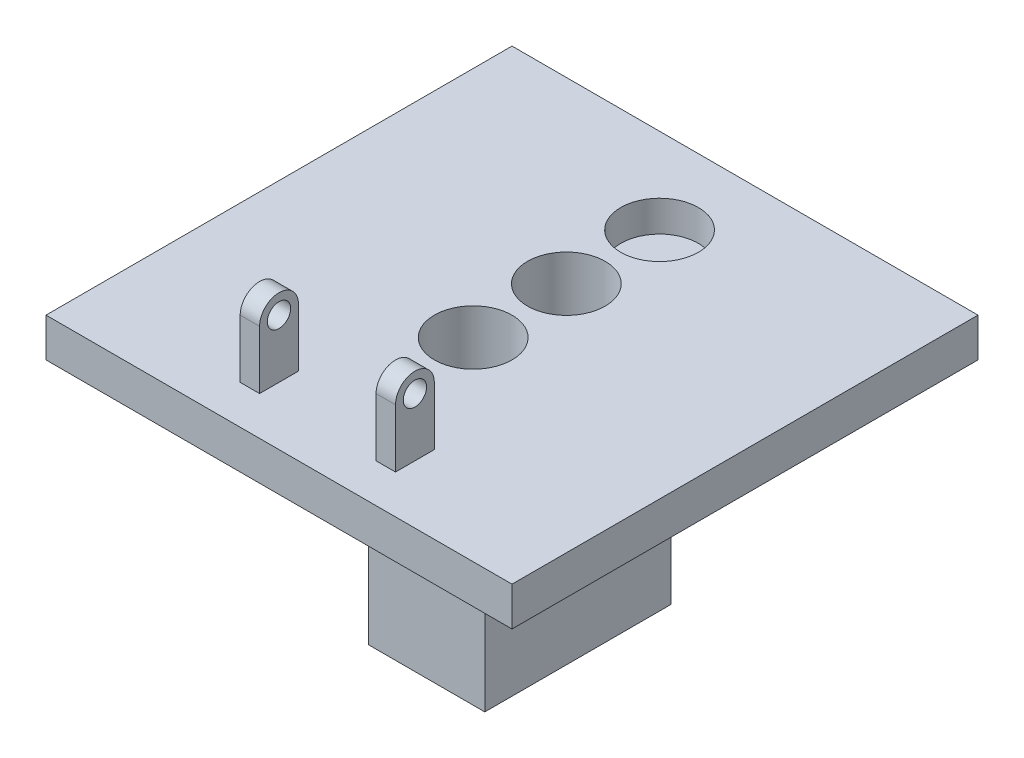
SolidWorks part; units mm, degrees
ref_plane "Front Plane" through (0, 0, 0) normal (0, 0, 1) x (1, 0, 0)
ref_plane "Top Plane" through (0, 0, 0) normal (0, 1, 0) x (1, 0, 0)
ref_plane "Right Plane" through (0, 0, 0) normal (1, 0, 0) x (0, 0, -1)
sketch "Sketch1" plane through (0, 0, 0) normal (0, 1, 0) x (1, 0, 0)
  line L1 (-76.2, 76.2) -> (76.2, 76.2)
  line L2 (-76.2, 76.2) -> (-76.2, -76.2)
  line L3 (-76.2, -76.2) -> (76.2, -76.2)
  line L4 (76.2, 76.2) -> (76.2, -76.2)
  line L5 (-76.2, 76.2) -> (76.2, -76.2) construction
  line L6 (-76.2, -76.2) -> (76.2, 76.2) construction
  point P0 (0, 0)
  dimension "D1" = 152.4
  dimension "D2" = 152.4
extrude "Boss-Extrude1" add sketch "Sketch1" along normal blind 12.7
sketch "Sketch2" plane through (0, 0, 0) normal (1, 0, 0) x (0, 0, -1)
  line L0 (-76.2, 12.7) -> (76.2, 12.7) construction
  line L1 (-63.5, 12.7) -> (-50.8, 12.7)
  line L2 (-63.5, 12.7) -> (-63.5, 38.1)
  line L3 (-63.5, 38.1) -> (-50.8, 38.1)
  line L4 (-50.8, 12.7) -> (-50.8, 38.1)
  line L6 (-76.2, 12.7) -> (-76.2, 0) construction
  dimension "D1" = 25.4
  dimension "D2" = 12.7
  dimension "D3" = 12.7
extrude "Boss-Extrude2" add sketch "Sketch2" along normal mid plane 50.8
fillet "Fillet1" 2 edges at (0, 38.1, 63.5) (0, 38.1, 50.8) type full round first side face at (0, 25.4, 63.5) second side face at (0, 25.4, 50.8) middle face at (0, 38.1, 57.15)
sketch "Sketch3" plane through (0, 0, 63.5) normal (0, 0, 1) x (1, 0, 0)
  line L0 (-76.2, 12.7) -> (76.2, 12.7) construction
  line L1 (-19.05, 12.7) -> (19.05, 12.7)
  line L2 (-19.05, 12.7) -> (-19.05, 48.2361)
  line L3 (-19.05, 48.2361) -> (19.05, 48.2361)
  line L4 (19.05, 12.7) -> (19.05, 48.2361)
  line L5 (-25.4, 31.75) -> (-25.4, 12.7) construction
  line L6 (25.4, 31.75) -> (25.4, 12.7) construction
  dimension "D1" = 6.35
  dimension "D2" = 6.35
extrude "Cut-Extrude1" cut sketch "Sketch3" against normal blind 50.8
sketch "Sketch4" plane through (25.4, 0, 0) normal (1, 0, 0) x (0, 0, -1)
  circle A0 centre (-57.15, 31.75) radius 3.81
  dimension "D1" = 7.62
extrude "Cut-Extrude2" cut sketch "Sketch4" against normal blind 50.8
sketch "Sketch5" plane through (0, 0, 0) normal (1, 0, 0) x (0, 0, -1)
  line L0 (-50.8, 12.7) -> (39.1205, 102.6205) construction
  line L1 (-76.2, 12.7) -> (76.2, 12.7) construction
  dimension "D1" = 45
ref_plane "Plane1" through (0, 31.75, 31.75) normal (0, 0.7071, 0.7071) x (0, 0.7071, -0.7071)
sketch "Sketch6" plane through (0, 12.7, 0) normal (0, 1, 0) x (1, 0, 0)
  line L0 (76.2, 76.2) -> (-76.2, 76.2) construction
  line L1 (-19.05, 76.2) -> (19.05, 76.2)
  line L2 (-19.05, 76.2) -> (-19.05, 0)
  line L3 (-19.05, 0) -> (19.05, 0)
  line L4 (19.05, 76.2) -> (19.05, 0)
  line L5 (-19.05, -63.5) -> (-19.05, -50.8) construction
  line L7 (19.05, -50.8) -> (19.05, -63.5) construction
  dimension "D1" = 76.2
extrude "Boss-Extrude3" [suppressed] add sketch "Sketch6" along normal up to surface (88.9 mm away)
sketch "Sketch7" plane through (0, 0, 0) normal (1, 0, 0) x (0, 0, -1)
  line L0 (76.2, 12.7) -> (76.2, 114.3)
  line L4 (76.2, 114.3) -> (0, 12.7)
  line L5 (-76.2, 12.7) -> (76.2, 12.7) construction
  line L6 (0, 12.7) -> (76.2, 12.7)
  dimension "D1" = 101.6
  dimension "D2" = 76.2
extrude "Boss-Extrude4" [suppressed] add sketch "Sketch7" along normal mid plane 38.1
sketch "Sketch9" [suppressed] plane through (0, 10.668, 14.224) normal (0, 0.6, 0.8) x (1, 0, 0)
  circle A0 centre (0, 31.0682) radius 16.51
  circle A1 centre (0, 69.1682) radius 16.51
  circle A2 centre (0, 107.2682) radius 16.51
  dimension "D1" = 33.02
  dimension "D2" = 3
sketch "Sketch11" plane through (0, 0, 0) normal (0, -1, 0) x (1, 0, 0)
  line L0 (-19.05, -33.02) -> (19.05, -33.02)
  line L5 (76.2, -76.2) -> (-76.2, -76.2) construction
  line L6 (-19.05, -60.96) -> (19.05, -60.96)
  line L7 (-19.05, -60.96) -> (-19.05, 27.94)
  line L9 (19.05, -60.96) -> (19.05, 27.94)
  line L10 (0, 63.9195) -> (0, -86.9628) construction
  line L11 (-19.05, -2.54) -> (19.05, -2.54)
  line L12 (-19.05, 27.94) -> (19.05, 27.94)
  dimension "D1" = 15.24
  dimension "D3" = 38.1
  dimension "D6" = 27.94
  dimension "D7" = 30.48
  dimension "D8" = 30.48
extrude "Boss-Extrude6" add sketch "Sketch11" along normal blind 76.2 contours L10 L11 L7 L0 | L11 L10 L0 L9 | L12 L10 L11 L9 | L10 L12 L7 L11 region at (-9.525, 0, -17.78) region at (9.525, 0, -17.78) region at (-9.525, 0, 12.7) region at (9.525, 0, 12.7)
sketch "Sketch14" plane through (0, 12.7, 0) normal (0, 1, 0) x (1, 0, 0)
  line L0 (76.2, 76.2) -> (-76.2, 76.2) construction
  line L1 (-19.05, 60.96) -> (19.05, 60.96) construction
  line L5 (0, 70.9023) -> (0, -46.5329) construction
  circle A0 centre (0, 48.26) radius 12.7
  circle A1 centre (0, 17.78) radius 12.7
  circle A2 centre (0, -12.7) radius 12.7
  dimension "D3" = 25.4
  dimension "D1" = 15.24
  dimension "D2" = 38.1
  dimension "D4" = 3
extrude "Cut-Extrude3" cut sketch "Sketch14" against normal blind 76.2 contours A1 | A2 region at (0, 12.7, -17.78) region at (0, 12.7, 12.7)
extrude "Cut-Extrude4" cut sketch "Sketch14<3>" against normal blind 10.16 contours A0 region at (0, 12.7, -48.26)
sketch "Sketch14<3>" plane through (0, 12.7, 0) normal (0, 1, 0) x (1, 0, 0) same geometry as "Sketch14"
